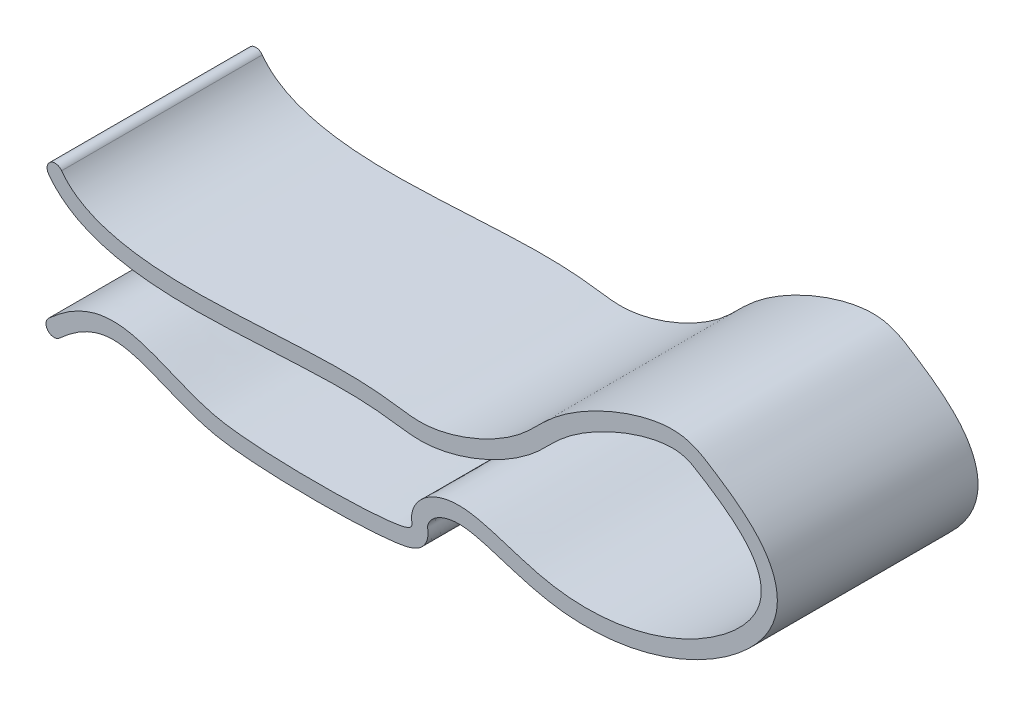
SolidWorks part; units mm, degrees
ref_plane "Front Plane" through (0, 0, 0) normal (0, 0, 1) x (1, 0, 0)
ref_plane "Top Plane" through (0, 0, 0) normal (0, 1, 0) x (1, 0, 0)
ref_plane "Right Plane" through (0, 0, 0) normal (1, 0, 0) x (0, 0, -1)
sketch "Sketch1" plane through (0, 0, 0) normal (0, 0, 1) x (1, 0, 0)
  line L0 (0, 0) -> (15, 0)
  line L1 (0, 2) -> (15, 2)
  line L2 (15, 0) -> (15, -2)
  line L3 (15, -2) -> (0, -2)
  line L4 (0, 0) -> (0, -2)
  line L5 (15, 2) -> (15, 4)
  line L6 (15, 4) -> (0, 4)
  line L7 (0, 4) -> (0, 2)
  arc A0 (-11.2404, -2.8872) -> (-12.0485, -2) centre (-11.6445, -2.4436) cw
  arc A1 (-12.0485, 7.3249) -> (-11.0768, 8.029) centre (-11.5626, 7.6769) cw
  spline S0 degree 3 poles (-12.0485, -2) (-7.5758, 2.0735) (-4.4119, -0.7417) (2.8083, -2.8181) (15.4344, -2.7032) (14.6477, -0.463) (17.494, 2.4814) (29.8748, -2.9176) (45.759, 5.9656) (38.7881, 10.9055) (34.2852, 13.6722) (27.6028, 11.0219) (23.097, 5.9273) (17.3102, 3.5572) (10.8669, 4.6886) (4.3541, 4.0059) (-9.4378, 3.7222) (-12.0485, 7.3249) knots 0 0 0 0 0.061998 0.069415 0.104581 0.116779 0.187001 0.227805 0.368832 0.522691 0.549819 0.630085 0.650123 0.730158 0.755961 0.882348 1 1 1 1
  spline S1 degree 1 poles (-11.2404, -2.8872) (-11.0768, 8.029) knots 0 0 1 1 construction
  spline S2 degree 3 poles (-11.2404, -2.8872) (-11.1157, -2.7736) (-10.8551, -2.5455) (-10.3691, -2.1563) (-9.7903, -1.7571) (-9.1507, -1.4113) (-8.3588, -1.0996) (-7.4575, -0.9409) (-6.3786, -1.0156) (-5.2088, -1.3224) (-3.922, -1.8127) (-2.7414, -2.3057) (-1.7131, -2.7032) (-0.9126, -2.9852) (-0.0085, -3.2557) (1.5378, -3.5527) (4.1835, -3.7706) (7.9129, -3.859) (10.9143, -3.7947) (12.9158, -3.6671) (14.143, -3.5296) (14.9152, -3.3764) (15.4705, -3.1486) (15.9108, -2.8422) (16.2597, -2.2885) (16.3243, -1.761) (16.2879, -1.4686) (16.2799, -1.41) (16.2788, -1.3858) (16.2787, -1.3369) (16.2856, -1.2725) (16.3071, -1.181) (16.3577, -1.0448) (16.468, -0.852) (16.6876, -0.6085) (17.1017, -0.2992) (17.8648, 0.0016) (19.1374, 0.0637) (20.9897, -0.4104) (23.2397, -1.1682) (25.7228, -1.7687) (28.1597, -1.9322) (30.5154, -1.7662) (33.4956, -1.1607) (36.8363, 0.1734) (39.9719, 2.3037) (41.6785, 4.2605) (42.3479, 5.9077) (42.5159, 7.5825) (41.8286, 9.4387) (40.5759, 10.8178) (39.433, 11.7685) (38.5428, 12.4151) (37.6367, 12.9999) (36.8298, 13.5494) (35.6965, 14.0506) (34.5543, 14.1345) (33.3846, 14.0443) (31.7953, 13.6811) (29.7694, 12.9263) (27.7544, 11.9048) (26.2123, 10.8798) (25.1238, 9.946) (24.2221, 9.0365) (23.2621, 8.1089) (21.7685, 7.0929) (19.5801, 5.9596) (17.5879, 5.3442) (16.1694, 5.1737) (15.3431, 5.1553) (14.3538, 5.2817) (13.0053, 5.4667) (11.2726, 5.5931) (9.0895, 5.6157) (6.253, 5.4922) (2.9724, 5.3142) (-1.0618, 5.1279) (-5.2924, 5.2718) (-8.3513, 5.9863) (-10.1527, 7.0062) (-10.8036, 7.652) (-11.0768, 8.029) knots 0 0 0 0 0.001953 0.003906 0.007812 0.011719 0.015625 0.023438 0.03125 0.039062 0.046875 0.054688 0.058594 0.0625 0.066406 0.070312 0.078125 0.085938 0.09375 0.097656 0.101562 0.105469 0.107422 0.109375 0.111328 0.113281 0.115234 0.117188 0.119141 0.121094 0.125 0.128906 0.132812 0.140625 0.148438 0.15625 0.171875 0.1875 0.203125 0.21875 0.234375 0.25 0.265625 0.28125 0.3125 0.34375 0.375 0.390625 0.40625 0.4375 0.46875 0.484375 0.5 0.515625 0.53125 0.546875 0.554688 0.5625 0.578125 0.59375 0.609375 0.625 0.632812 0.640625 0.65625 0.671875 0.6875 0.71875 0.726562 0.734375 0.75 0.765625 0.78125 0.8125 0.84375 0.875 0.90625 0.9375 0.96875 0.984375 1 1 1 1
  dimension "D2" = 2
  dimension "D1" = 15
  dimension "D3" = 2
  dimension "D4" = 1.2
extrude "Boss-Extrude3" add sketch "Sketch1" along normal blind 15 contours S0 A1 S2 A0
